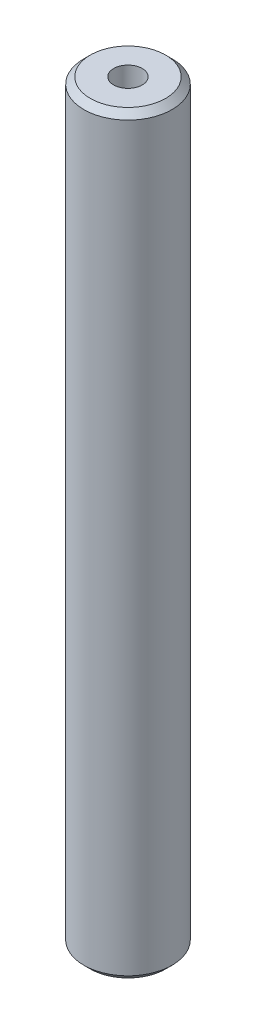
SolidWorks part; units mm, degrees
ref_plane "Front Plane" through (0, 0, 0) normal (0, 0, 1) x (1, 0, 0)
ref_plane "Top Plane" through (0, 0, 0) normal (0, 1, 0) x (1, 0, 0)
ref_plane "Right Plane" through (0, 0, 0) normal (1, 0, 0) x (0, 0, -1)
sketch "Sketch1" plane through (0, 0, 0) normal (0, 1, 0) x (1, 0, 0)
  circle A0 centre (0, 0) radius 7.5
  dimension "SHAFT_OD" = 15
extrude "Boss-Extrude1" add sketch "Sketch1" along normal blind 128.3021
sketch "Sketch2" plane through (0, 0, 0) normal (0, 1, 0) x (1, 0, 0)
  circle A0 centre (0, 0) radius 2.4334
  dimension "BORE_D" = 4.8668
extrude "Cut-Extrude1" cut sketch "Sketch2" along normal through all
chamfer "Chamfer1" distance 1.0951 angle 45 2 edges at (0, 128.3021, 7.5) (0, 0, 7.5)
